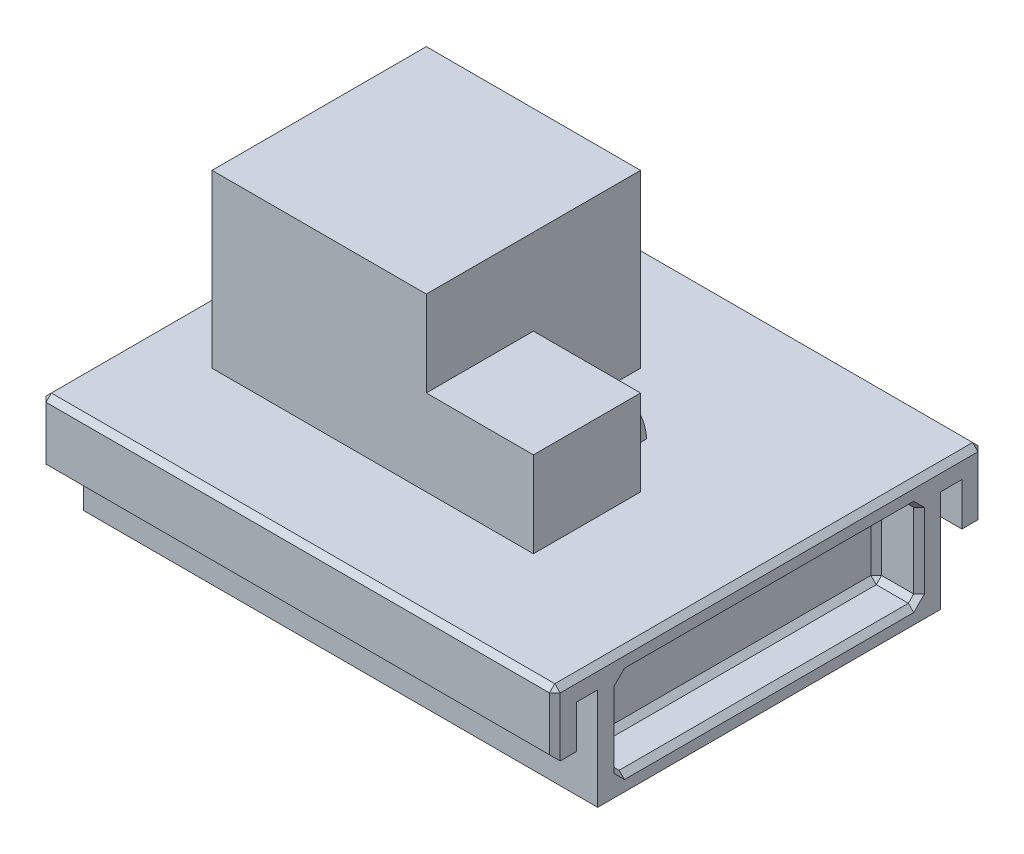
SolidWorks part; units mm, degrees
note: The reader was unsure of these and kept them because the rebuilt part matched: shared geometry of "Sketch2<3>".
ref_plane "Płaszczyzna przednia" through (0, 0, 0) normal (0, 0, 1) x (1, 0, 0)
ref_plane "Płaszczyzna górna" through (0, 0, 0) normal (0, 1, 0) x (1, 0, 0)
ref_plane "Płaszczyzna prawa" through (0, 0, 0) normal (1, 0, 0) x (0, 0, -1)
sketch "Sketch1" plane through (0, 0, 0) normal (1, 0, 0) x (0, 0, -1)
  line L0 (0, 0) -> (0, 30.7022) construction
  line L1 (0, 0) -> (-40, 0) construction
  line L2 (-40, 0) -> (-45, 0)
  line L3 (-45, 0) -> (-45, -10)
  line L4 (-45, -10) -> (-50, -10)
  line L5 (-50, -10) -> (-50, 5)
  line L6 (-50, 5) -> (50, 5)
  line L7 (-40, 0) -> (-40, -25)
  line L8 (-40, -25) -> (40, -25)
  line L9 (45, 0) -> (45, -10)
  line L10 (50, -10) -> (50, 5)
  line L11 (45, -10) -> (50, -10)
  line L12 (40, 0) -> (45, 0)
  line L13 (40, 0) -> (40, -25)
  point P14 (0, 5)
  point P17 (0, -25)
  dimension "D1" = 40
  dimension "D2" = 5
  dimension "D3" = 10
  dimension "D4" = 5
  dimension "D5" = 15
  dimension "D6" = 50
  dimension "D7" = 25
extrude "Boss-Extrude1" add sketch "Sketch1" along normal mid plane 120
sketch "Sketch2" plane through (0, 5, 0) normal (0, 1, 0) x (1, 0, 0)
  line L0 (-60, 50) -> (60, -50) construction
  line L1 (60, -50) -> (60, 50) construction
  line L2 (60, 50) -> (-60, -50) construction
  line L3 (-60, -50) -> (60, -50) construction
  line L4 (-60, -50) -> (-60, 50) construction
  line L5 (-60, 50) -> (60, 50) construction
  line L7 (5, -25) -> (-45, -25)
  line L8 (5, -25) -> (5, 25)
  line L9 (5, 25) -> (-45, 25)
  line L10 (-45, -25) -> (-45, 25)
  line L11 (5, -25) -> (-45, 25) construction
  line L12 (5, 25) -> (-45, -25) construction
  line L13 (30, -25) -> (5, -25)
  line L14 (30, -25) -> (30, 0)
  line L15 (30, 0) -> (5, 0)
  line L16 (5, -25) -> (5, 0)
  line L17 (30, -25) -> (5, 0) construction
  line L18 (30, 0) -> (5, -25) construction
  point P4 (-20, 0)
  point P15 (17.5, -12.5)
  dimension "D1" = 100
  dimension "D2" = 120
  dimension "D3" = 50
  dimension "D4" = 50
  dimension "D5" = 20
  dimension "D6" = 15
  dimension "D7" = 25
  dimension "D8" = 25
extrude "Boss-Extrude2" add sketch "Sketch2" along normal blind 40 contours L10 L7 L8 L9
extrude "Boss-Extrude3" add sketch "Sketch2<3>" along normal blind 20 contours L14 L15 L8 L13
sketch "Sketch2<3>" plane through (0, 5, 0) normal (0, 1, 0) x (1, 0, 0) same geometry as "Sketch2"
sketch "Sketch3" plane through (0, 0, 0) normal (0, 0, -1) x (-1, 0, 0)
  line L0 (-30, 25) -> (-5, 5) construction
  line L1 (-30, 5) -> (-5, 25) construction
  line L2 (-5, 45) -> (-5, 5) construction
  line L3 (-30, 5) -> (-5, 5) construction
  line L4 (-17.5, 17.8868) -> (-20, 16.4434)
  line L5 (-20, 16.4434) -> (-20, 13.5566)
  line L6 (-20, 13.5566) -> (-17.5, 12.1132)
  line L7 (-17.5, 12.1132) -> (-15, 13.5566)
  line L8 (-15, 13.5566) -> (-15, 16.4434)
  line L9 (-15, 16.4434) -> (-17.5, 17.8868)
  line L10 (-5, 25) -> (-5, 5) construction
  circle A0 centre (-17.5, 15) radius 2.5 construction
  dimension "D1" = 5
  dimension "D2" = 10
  dimension "D3" = 12.5
sketch "Sketch4" plane through (0, 5, 0) normal (0, 1, 0) x (1, 0, 0)
  line L0 (17.5, 0) -> (17.5, 10) construction
  line L1 (17.5, 0) -> (15, 0) construction
  line L2 (20, 0) -> (17.5, 0) construction
  line L3 (5, 0) -> (5, 25) construction
  line L4 (17.5, 12.8868) -> (15, 11.4434)
  line L5 (15, 11.4434) -> (15, 8.5566)
  line L6 (15, 8.5566) -> (17.5, 7.1132)
  line L7 (17.5, 7.1132) -> (20, 8.5566)
  line L8 (20, 8.5566) -> (20, 11.4434)
  line L9 (20, 11.4434) -> (17.5, 12.8868)
  circle A0 centre (17.5, 10) radius 2.5 construction
  dimension "D2" = 5
  dimension "D1" = 10
  dimension "D3" = 12.5
ref_plane "Plane1" through (17.5, 0, 0) normal (1, 0, 0) x (0, 0, -1)
sketch "Sketch5" plane through (17.5, 0, 0) normal (1, 0, 0) x (0, 0, -1)
  line L0 (0, 16.4434) -> (0, 13.5566) construction
  line L1 (12.5, 5) -> (7.5, 5) construction
  arc A0 (0, 15) -> (10, 5) centre (0, 5) cw
ref_plane "Plane2" through (0, 2.5, 2.5) normal (0, 0.7071, 0.7071) x (1, 0, 0)
sketch "Sketch6" plane through (0, 2.5, 2.5) normal (0, 0.7071, 0.7071) x (1, 0, 0)
  line L1 (17.5, 16.4223) -> (15, 14.9789)
  line L2 (15, 14.9789) -> (15, 12.0922)
  line L3 (15, 12.0922) -> (17.5, 10.6488)
  line L4 (17.5, 10.6488) -> (20, 12.0922)
  line L5 (20, 12.0922) -> (20, 14.9789)
  line L6 (20, 14.9789) -> (17.5, 16.4223)
  circle A0 centre (17.5, 13.5355) radius 2.5 construction
  dimension "D1" = 5
loft "Loft3" add profiles "Sketch3", "Sketch6", "Sketch4"
sketch "Sketch7" plane through (60, 0, 0) normal (1, 0, 0) x (0, 0, -1)
  line L24 (-35, 0) -> (-35, -20)
  line L25 (-35, -20) -> (35, -20)
  line L26 (35, -20) -> (35, 0)
  line L27 (35, 0) -> (-35, 0)
  line L28 (-35, 0) -> (-35, -20)
  line L29 (-35, -20) -> (35, -20)
  line L30 (35, -20) -> (35, 0)
  line L31 (35, 0) -> (-35, 0)
  dimension "D1" = 5
extrude "Cut-Extrude1" cut sketch "Sketch7" against normal blind 10
mirror "Mirror1" about plane through (0, 0, 0) normal (1, 0, 0) of "Cut-Extrude1"
sketch "Sketch8" plane through (0, -25, 0) normal (0, -1, 0) x (1, 0, 0)
  line L0 (-60, 40) -> (60, -40) construction
  line L1 (-60, -40) -> (60, 40) construction
  line L3 (-20, -10) -> (20, -10)
  line L4 (-20, -10) -> (-20, 10)
  line L5 (-20, 10) -> (20, 10)
  line L6 (20, -10) -> (20, 10)
  line L7 (-20, -10) -> (20, 10) construction
  line L8 (-20, 10) -> (20, -10) construction
  line L9 (5, -2.5) -> (-5, -2.5)
  line L10 (5, -2.5) -> (5, 2.5)
  line L11 (5, 2.5) -> (-5, 2.5)
  line L12 (-5, -2.5) -> (-5, 2.5)
  line L13 (5, -2.5) -> (-5, 2.5) construction
  line L14 (5, 2.5) -> (-5, -2.5) construction
  point P8 (0, 0)
  point P13 (0, 0)
  dimension "D1" = 20
  dimension "D2" = 40
  dimension "D3" = 10
  dimension "D4" = 5
extrude "Boss-Extrude4" add sketch "Sketch8" along normal blind 5 contours L10 L9 L12 L11
chamfer "Chamfer1" distance 1.25 angle 45 36 edges at (60, -20, 0) (60, 0, 0) (55, 0, 35) (60, -10, 35) (55, -20, 35) (55, -20, -35) (60, -10, -35) (55, 0, -35) (50, -10, -35) (50, -20, 0) (50, -10, 35) (50, 0, 0) (-55, -20, 35) (-50, -10, 35) (-55, 0, 35) (-60, -10, 35) (-60, 0, 0) (-60, -20, 0) (-55, 0, -35) (-50, -10, -35) (-55, -20, -35) (-60, -10, -35) (60, -25, 0) (0, -25, -40) (0, -25, 40) (-60, -25, 0) (0, -10, 50) (0, -10, -50) (-60, -2.5, 50) (-60, -2.5, -50) (60, -2.5, -50) (60, -2.5, 50) (-60, 5, 0) (0, 5, 50) (60, 5, 0) (0, 5, -50)
